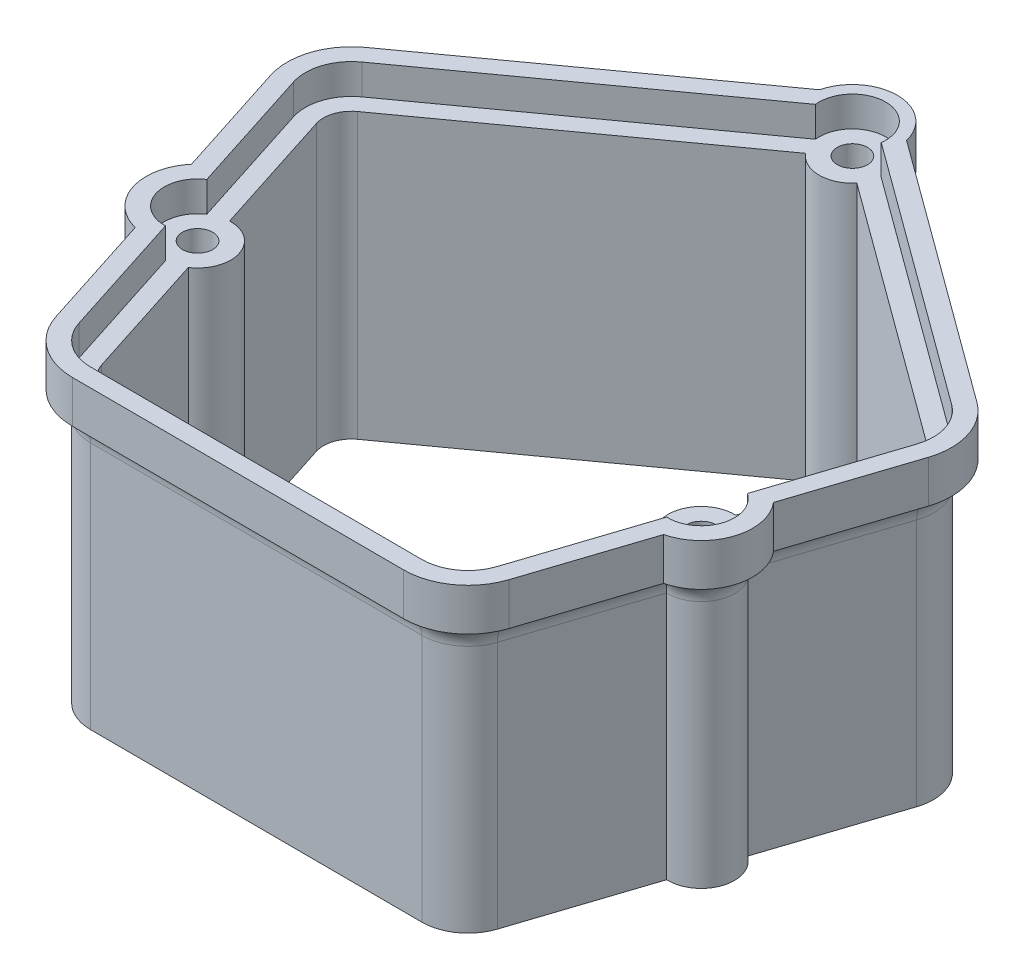
SolidWorks part; units mm, degrees
material "ABS"
ref_plane "Front Plane" through (0, 0, 0) normal (0, 0, 1) x (1, 0, 0)
ref_plane "Top Plane" through (0, 0, 0) normal (0, 1, 0) x (1, 0, 0)
ref_plane "Right Plane" through (0, 0, 0) normal (1, 0, 0) x (0, 0, -1)
sketch "Sketch1" plane through (0, 0, 0) normal (0, 1, 0) x (1, 0, 0)
  line L0 (0.1648, 51.4055) -> (0.1744, 54.4055) construction
  line L1 (-48.8478, 13.1866) -> (-42.0527, -7.9568)
  line L2 (-27.636, -42.3821) -> (27.3637, -42.5584)
  line L3 (31.7678, -39.3802) -> (38.6983, -18.2808)
  line L4 (47.2696, 18.0438) -> (4.4052, 49.397)
  line L5 (-4.0885, 49.4243) -> (-47.1529, 18.3465)
  line L6 (-51.7039, 12.2687) -> (-44.9089, -8.8747)
  line L7 (-27.6456, -45.3821) -> (27.3541, -45.5584)
  line L8 (34.618, -40.3164) -> (41.5485, -19.217)
  line L9 (49.0407, 20.4652) -> (5.6267, 52.2204)
  line L10 (-5.2919, 52.2554) -> (-48.9085, 20.7792)
  line L11 (-40.4337, -12.9946) -> (-43.2898, -13.9125) construction
  line L12 (40.3496, -13.2535) -> (43.1998, -14.1897) construction
  line L13 (44.851, -9.1625) -> (51.7815, 11.937)
  line L14 (42.0009, -8.2263) -> (48.9313, 12.8732)
  line L15 (-41.6708, -18.9502) -> (-34.8757, -40.0936)
  line L16 (-38.8147, -18.0323) -> (-32.0196, -39.1757)
  circle A0 centre (0, 0) radius 42.4705 construction
  arc A1 (-32.0196, -39.1757) -> (-27.636, -42.3821) centre (-27.6212, -37.7622) ccw
  arc A2 (27.3637, -42.5584) -> (31.7678, -39.3802) centre (27.3785, -37.9385) ccw
  arc A3 (48.9313, 12.8732) -> (47.2696, 18.0438) centre (44.542, 14.3149) ccw
  arc A5 (-48.8478, 13.1866) -> (-47.1529, 18.3465) centre (-44.4494, 14.6002) cw
  circle A6 centre (0, 0) radius 45.4705 construction
  arc A7 (-34.8757, -40.0936) -> (-27.6456, -45.3821) centre (-27.6212, -37.7622) ccw
  arc A8 (27.3541, -45.5584) -> (34.618, -40.3164) centre (27.3785, -37.9385) ccw
  arc A9 (51.7815, 11.937) -> (49.0407, 20.4652) centre (44.542, 14.3149) ccw
  arc A11 (-51.7039, 12.2687) -> (-48.9085, 20.7792) centre (-44.4494, 14.6002) cw
  circle A12 centre (0.1696, 52.9055) radius 2.5
  circle A13 centre (-41.8618, -13.4535) radius 2.5
  circle A14 centre (41.7747, -13.7216) radius 2.5
  circle A15 centre (0.1696, 52.9055) radius 5.5
  circle A16 centre (-41.8618, -13.4535) radius 5.5
  circle A17 centre (41.7747, -13.7216) radius 5.5
  dimension "D1" = 4.62
  dimension "D3" = 7.62
  dimension "D5" = 5
  dimension "D6" = 5
  dimension "D7" = 5
  dimension "D8" = 3
  dimension "D2" = 3
  dimension "D4" = 3
extrude "Boss-Extrude1" add sketch "Sketch1" along normal blind 46.99 contours A17 L3 A2 L2 A1 L16 A16 L15 A7 L7 A8 L8 | A17 A14 | A17 L13 A9 L9 A15 L4 A3 L14 | A16 A13 | A16 L1 A5 L5 A15 L10 A11 L6 | A15 A12
sketch "Sketch2" plane through (0, 46.99, 0) normal (0, 1, 0) x (1, 0, 0)
  line L0 (-5.2919, 52.2554) -> (-7.0474, 54.6881)
  line L1 (-7.0474, 54.6881) -> (-50.6641, 23.2119)
  line L2 (0.1872, 58.4055) -> (0.1934, 60.3394)
  line L3 (0.1872, 58.4055) -> (-0.1457, -45.4703) construction
  line L4 (-51.7039, 12.2687) -> (-54.5601, 11.3508)
  line L5 (-48.9085, 20.7792) -> (-50.6641, 23.2119)
  line L6 (-54.5601, 11.3508) -> (-48.3523, -7.9651)
  line L7 (49.0407, 20.4652) -> (5.6267, 52.2204)
  line L8 (-5.2919, 52.2554) -> (-48.9085, 20.7792)
  line L9 (-51.7039, 12.2687) -> (-44.9089, -8.8747)
  line L10 (-41.6708, -18.9502) -> (-34.8757, -40.0936)
  line L11 (-27.6456, -45.3821) -> (27.3541, -45.5584)
  line L12 (34.618, -40.3164) -> (41.5485, -19.217)
  line L13 (44.851, -9.1625) -> (51.7815, 11.937)
  line L14 (49.0407, 20.4652) -> (5.6267, 52.2204)
  line L15 (-5.2919, 52.2554) -> (-48.9085, 20.7792)
  line L16 (-51.7039, 12.2687) -> (-44.9089, -8.8747)
  line L17 (-41.6708, -18.9502) -> (-34.8757, -40.0936)
  line L19 (34.618, -40.3164) -> (41.5485, -19.217)
  line L20 (44.851, -9.1625) -> (51.7815, 11.937)
  line L21 (-34.8757, -40.0936) -> (-37.7319, -41.0115) construction
  line L22 (5.6267, 52.2204) -> (7.3979, 54.6418)
  line L23 (-37.7319, -41.0115) -> (-43.9396, -21.6956)
  line L24 (-0.1457, -48.4703) -> (-27.6552, -48.3821)
  line L25 (-27.6456, -45.3821) -> (27.3541, -45.5584) construction
  line L26 (-27.6456, -45.3821) -> (-0.1457, -45.4703)
  line L27 (7.3979, 54.6418) -> (50.8118, 22.8866)
  line L28 (54.6317, 11.0008) -> (48.3003, -8.2749)
  line L29 (37.4682, -41.2526) -> (43.7996, -21.9769)
  line L30 (27.3541, -45.5584) -> (-0.1457, -45.4703)
  line L31 (-0.165, -48.4702) -> (27.3445, -48.5584)
  line L32 (49.0407, 20.4652) -> (50.8118, 22.8866)
  line L33 (51.7815, 11.937) -> (54.6317, 11.0008)
  line L34 (-5.2919, 52.2554) -> (-7.0474, 54.6881)
  arc A1 (-48.3523, -7.9651) -> (-43.9396, -21.6956) centre (-41.8618, -13.4535) ccw
  arc A2 (-54.5601, 11.3508) -> (-50.6641, 23.2119) centre (-44.4494, 14.6002) cw
  arc A3 (-27.6552, -48.3821) -> (-37.7319, -41.0115) centre (-27.6212, -37.7622) cw
  arc A5 (54.6317, 11.0008) -> (50.8118, 22.8866) centre (44.542, 14.3149) ccw
  arc A6 (48.3003, -8.2749) -> (43.7996, -21.9769) centre (41.7747, -13.7216) cw
  arc A7 (5.6267, 52.2204) -> (-5.2919, 52.2554) centre (0.1696, 52.9055) ccw
  arc A8 (-48.9085, 20.7792) -> (-51.7039, 12.2687) centre (-44.4494, 14.6002) ccw
  arc A9 (-44.9089, -8.8747) -> (-41.6708, -18.9502) centre (-41.8618, -13.4535) ccw
  arc A10 (-34.8757, -40.0936) -> (-27.6456, -45.3821) centre (-27.6212, -37.7622) ccw
  arc A11 (27.3541, -45.5584) -> (34.618, -40.3164) centre (27.3785, -37.9385) ccw
  arc A12 (41.5485, -19.217) -> (44.851, -9.1625) centre (41.7747, -13.7216) ccw
  arc A13 (51.7815, 11.937) -> (49.0407, 20.4652) centre (44.542, 14.3149) ccw
  arc A14 (5.6267, 52.2204) -> (-5.2919, 52.2554) centre (0.1696, 52.9055) ccw
  arc A15 (-48.9085, 20.7792) -> (-51.7039, 12.2687) centre (-44.4494, 14.6002) ccw
  arc A16 (-44.9089, -8.8747) -> (-41.6708, -18.9502) centre (-41.8618, -13.4535) ccw
  arc A17 (-34.8757, -40.0936) -> (-27.6456, -45.3821) centre (-27.6212, -37.7622) ccw
  arc A18 (27.3541, -45.5584) -> (34.618, -40.3164) centre (27.3785, -37.9385) ccw
  arc A19 (41.5485, -19.217) -> (44.851, -9.1625) centre (41.7747, -13.7216) ccw
  arc A20 (51.7815, 11.937) -> (49.0407, 20.4652) centre (44.542, 14.3149) ccw
  arc A21 (27.3445, -48.5584) -> (37.4682, -41.2526) centre (27.3785, -37.9385) ccw
  arc A22 (-7.0474, 54.6881) -> (7.4093, 54.5936) centre (0.1696, 52.9055) cw
  dimension "D6" = 3
  dimension "D2" = 3
  dimension "D3" = 3
  dimension "D4" = 3
  dimension "D5" = 3
  dimension "D1" = 0
extrude "Boss-Extrude7" add sketch "Sketch2" along normal blind 5 and the other way blind 2
fillet "Fillet1" radius 4 14 edges at (-47.098, 44.99, 15.1363) (48.3163, 44.99, -1.3873) (51.7966, 44.99, -16.6464) (-27.1002, 44.99, -36.5173) (-51.6888, 44.99, -16.9781) (38.0832, 44.99, 29.7667) (31.8377, 44.99, 44.1175) (-0.1457, 44.99, 45.4703) (-32.1198, 44.99, 43.9125) (47, 44.99, 15.438) (0.1872, 44.99, -58.4055) (27.3337, 44.99, -36.3428) (-48.3064, 44.99, -1.697) (-38.2733, 44.99, 29.5219)
